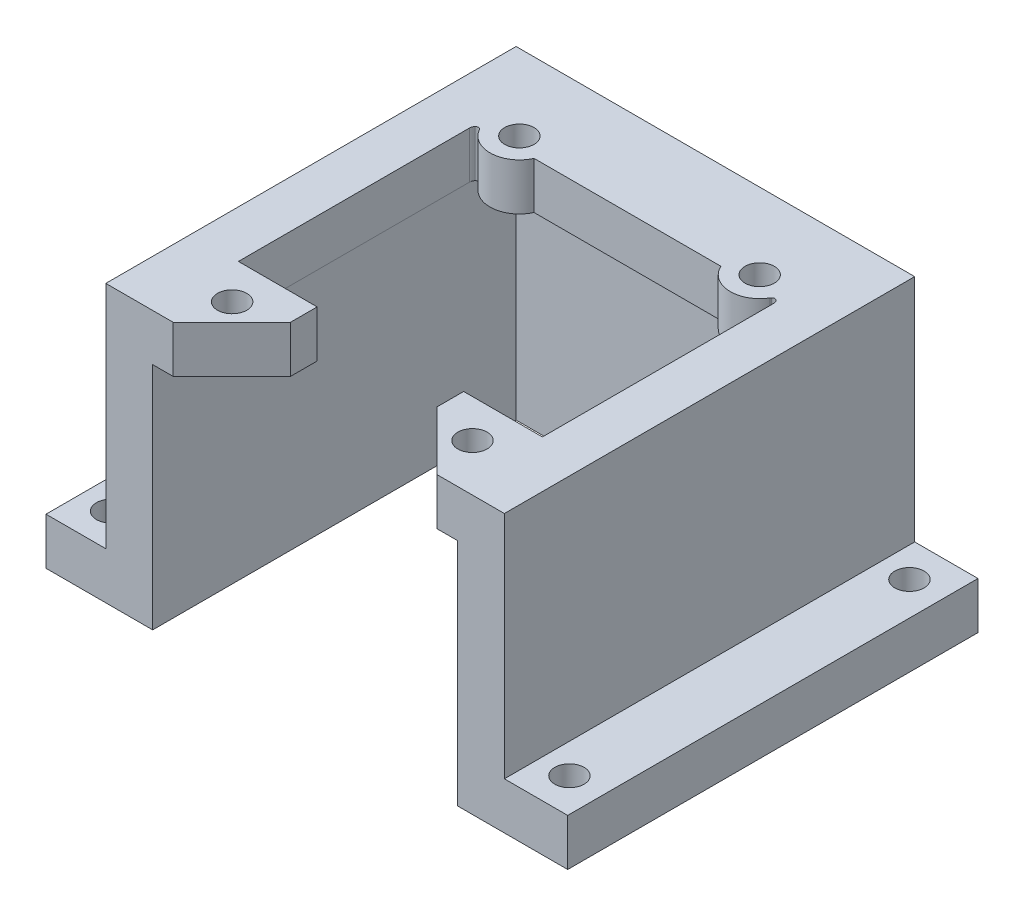
SolidWorks part; units mm, degrees
ref_plane "Front Plane" through (0, 0, 0) normal (0, 0, 1) x (1, 0, 0)
ref_plane "Top Plane" through (0, 0, 0) normal (0, 1, 0) x (1, 0, 0)
ref_plane "Right Plane" through (0, 0, 0) normal (1, 0, 0) x (0, 0, -1)
sketch "Sketch1" plane through (0, 0, 0) normal (0, 1, 0) x (1, 0, 0)
  line L1 (0, 0) -> (44.5, 0)
  line L2 (0, 0) -> (0, 35)
  line L3 (0, 35) -> (44.5, 35)
  line L4 (44.5, 0) -> (44.5, 35)
  dimension "D1" = 44.5
  dimension "D2" = 35
extrude "Boss-Extrude1" add sketch "Sketch1" along normal blind 4
sketch "Sketch3" plane through (0, 0, 0) normal (0, 1, 0) x (1, 0, 0)
  line L0 (44.5, 35) -> (0, 35) construction
  line L2 (9.1, 31) -> (9.1, 0)
  line L4 (35.1, 31) -> (35.1, 0)
  line L7 (39.1, 35) -> (39.1, 0)
  line L9 (5.1, 35) -> (5.1, 0)
  line L10 (0, 0) -> (44.5, 0) construction
  line L13 (35.1, 31) -> (9.1, 31)
  line L15 (5.1, 35) -> (39.1, 35)
  line L16 (9.1, 0) -> (5.1, 0)
  line L17 (35.1, 0) -> (39.1, 0)
  dimension "D1" = 5.4
  dimension "D2" = 4
  dimension "D3" = 26
  dimension "D6" = 4
extrude "Boss-Extrude2" add sketch "Sketch3" along normal blind 19.6
sketch "Sketch4" plane through (0, 4, 0) normal (0, 1, 0) x (1, 0, 0)
  line L4 (9.1, 31) -> (9.1, 0)
  line L5 (9.1, 0) -> (35.1, 0)
  line L6 (35.1, 0) -> (35.1, 31)
  line L7 (35.1, 31) -> (9.1, 31)
  line L9 (9.1, 0) -> (35.1, 0)
  line L10 (35.1, 0) -> (35.1, 31)
  line L11 (35.1, 31) -> (9.1, 31)
  line L13 (9.1, 31) -> (9.1, 0)
  dimension "D1" = 0
extrude "Cut-Extrude1" cut sketch "Sketch4" against normal blind 4
sketch "Sketch5" plane through (0, 19.6, 0) normal (0, 1, 0) x (1, 0, 0)
  line L0 (15.85, 0) -> (5.1, 0)
  line L1 (39.1, 0) -> (28.35, 0)
  line L2 (39.1, 0) -> (39.1, 35)
  line L3 (39.1, 35) -> (5.1, 35)
  line L4 (5.1, 0) -> (5.1, 35)
  line L6 (15.85, 0) -> (15.85, 7.2772)
  line L8 (28.35, 0) -> (28.35, 7.2772)
  line L9 (22.1, -965) -> (22.1, 49035) construction
  line L10 (35.0659, 27.5) -> (9.1341, 27.5)
  line L11 (35.0659, 27.5) -> (35.0659, 7.2772)
  line L12 (35.0659, 7.2772) -> (28.35, 7.2772)
  line L13 (9.1341, 27.5) -> (9.1341, 7.2772)
  line L14 (15.85, 7.2772) -> (9.1341, 7.2772)
  point P17 (22.1, 35)
  point P20 (22.1, 27.5)
  dimension "D1" = 12.5
  dimension "D2" = 7.5
  dimension "D3" = 20.2228
extrude "Boss-Extrude3" add sketch "Sketch5" along normal blind 4
chamfer "Chamfer1" distance 5 angle 45 2 edges at (15.85, 21.6, 0) (28.35, 21.6, 0)
sketch "Sketch6" plane through (0, 23.6, 0) normal (0, 1, 0) x (1, 0, 0)
  line L0 (22.1, 27.5) -> (22.1, 10.9812)
  line L1 (9.1341, 27.5) -> (35.0659, 27.5) construction
  line L2 (15.85, 7.2772) -> (9.1341, 7.2772) construction
  circle A0 centre (11.85, 4.0272) radius 1.25
  circle A1 centre (32.35, 4.0272) radius 1.25
  circle A2 centre (32.35, 28.5272) radius 1.25
  circle A3 centre (11.85, 28.5272) radius 1.25
  point P12 (0, 0)
  line M8 (9.1341, 27.5) -> (35.0659, 27.5)
  dimension "D1" = 2.5
  dimension "D4" = 10.25
  dimension "D5" = 3.25
  dimension "D2" = 2
  dimension "D3" = 2
extrude "Cut-Extrude2" cut sketch "Sketch6" against normal through all both and the other way through all contours A0 | A1 | A3 M8 | A2 M8 region at (11.85, 23.6, -4.0272) region at (32.35, 23.6, -4.0272) region at (32.35, 23.6, -28.5785) region at (11.85, 23.6, -28.5785)
sketch "Sketch7" plane through (0, 23.6, 0) normal (0, 1, 0) x (1, 0, 0)
  circle A0 centre (11.85, 28.5272) radius 1.25
  circle A1 centre (11.85, 28.5272) radius 2.5
  circle A3 centre (32.35, 28.5272) radius 2.5
  circle A4 centre (32.35, 28.5272) radius 1.25
  dimension "D1" = 5
  dimension "D2" = 5
extrude "Boss-Extrude4" add sketch "Sketch7" against normal up to surface (4 mm away) up to face at (32.35, 19.6, -2.7772)
fillet "Fillet1" radius 0.5 4 edges at (35.0659, 21.6, -27.5) (9.1341, 21.6, -27.5) (34.6292, 21.6, -27.5) (9.5708, 21.6, -27.5)
fillet "Fillet3" radius 0.25 2 edges at (9.451, 21.6, -27.4653) (34.749, 21.6, -27.4653)
sketch "Sketch8" plane through (0, 4, 0) normal (0, 1, 0) x (1, 0, 0)
  line L1 (0, 35) -> (0, 0) construction
  line L2 (5.1, 35) -> (0, 35) construction
  line L3 (22.1, 35) -> (22.1, 21.6841)
  line L4 (39.1, 35) -> (5.1, 35) construction
  line L5 (0, 0) -> (5.1, 0) construction
  circle A0 centre (2.55, 32) radius 1.25
  circle A1 centre (41.65, 32) radius 1.25
  circle A2 centre (2.55, 3) radius 1.25
  circle A3 centre (41.65, 3) radius 1.25
  dimension "D1" = 2.5
  dimension "D2" = 2.55
  dimension "D3" = 3
  dimension "D5" = 3
  dimension "D4" = 2
extrude "Cut-Extrude3" cut sketch "Sketch8" against normal through all both and the other way through all contours A0 | A1 | A2 | A3 region at (2.55, 4, -32)
